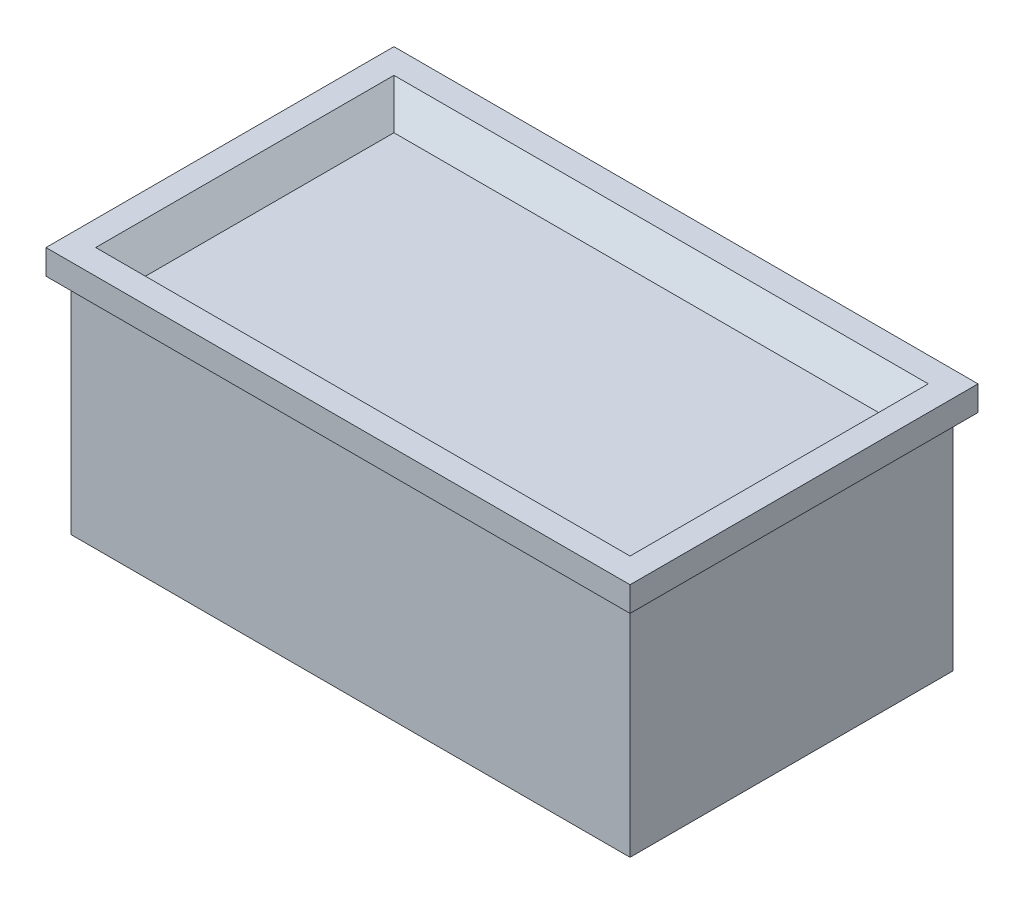
SolidWorks part; units mm, degrees
ref_plane "前视基准面" through (0, 0, 0) normal (0, 0, 1) x (1, 0, 0)
ref_plane "上视基准面" through (0, 0, 0) normal (0, 1, 0) x (1, 0, 0)
ref_plane "右视基准面" through (0, 0, 0) normal (1, 0, 0) x (0, 0, -1)
sketch "草图1" plane through (0, 0, 0) normal (0, 1, 0) x (1, 0, 0)
  line L1 (22.5, -13) -> (-22.5, -13)
  line L2 (22.5, -13) -> (22.5, 13)
  line L3 (22.5, 13) -> (-22.5, 13)
  line L4 (-22.5, -13) -> (-22.5, 13)
  line L5 (22.5, -13) -> (-22.5, 13) construction
  line L6 (22.5, 13) -> (-22.5, -13) construction
  point P0 (0, 0)
  dimension "D1" = 45
  dimension "D2" = 26
extrude "凸台-拉伸1" add sketch "草图1" along normal blind 18
sketch "草图2" plane through (0, 18, 0) normal (0, 1, 0) x (1, 0, 0)
  line L1 (23.5, -14) -> (-23.5, -14)
  line L2 (23.5, -14) -> (23.5, 14)
  line L3 (23.5, 14) -> (-23.5, 14)
  line L4 (-23.5, -14) -> (-23.5, 14)
  line L5 (23.5, -14) -> (-23.5, 14) construction
  line L6 (23.5, 14) -> (-23.5, -14) construction
  point P0 (0, 0)
  dimension "D1" = 47
  dimension "D2" = 28
extrude "凸台-拉伸2" add sketch "草图2" along normal blind 2 contours L3 L4 L1 L2
sketch "草图3" plane through (0, 20, 0) normal (0, 1, 0) x (1, 0, 0)
  line L0 (19.5, -10) -> (19.5, 10)
  line L1 (19.5, 10) -> (-19.5, 10)
  line L2 (-19.5, 10) -> (-19.5, -10)
  line L3 (-19.5, -10) -> (19.5, -10)
  line L4 (23.5, -14) -> (23.5, 14)
  line L5 (23.5, 14) -> (-23.5, 14)
  line L6 (-23.5, 14) -> (-23.5, -14)
  line L7 (-23.5, -14) -> (23.5, -14)
  line L8 (23.5, -14) -> (23.5, 14) construction
  line L9 (23.5, 14) -> (-23.5, 14) construction
  line L10 (-23.5, 14) -> (-23.5, -14) construction
  line L11 (-23.5, -14) -> (23.5, -14) construction
  dimension "D1" = 0
  dimension "D2" = 4
extrude "切除-拉伸2" cut sketch "草图3" against normal blind 2
chamfer "倒角1" distance 2 distance2 2 4 edges at (-19.5, 20, 0) (0, 20, 10) (19.5, 20, 0) (0, 20, -10)
